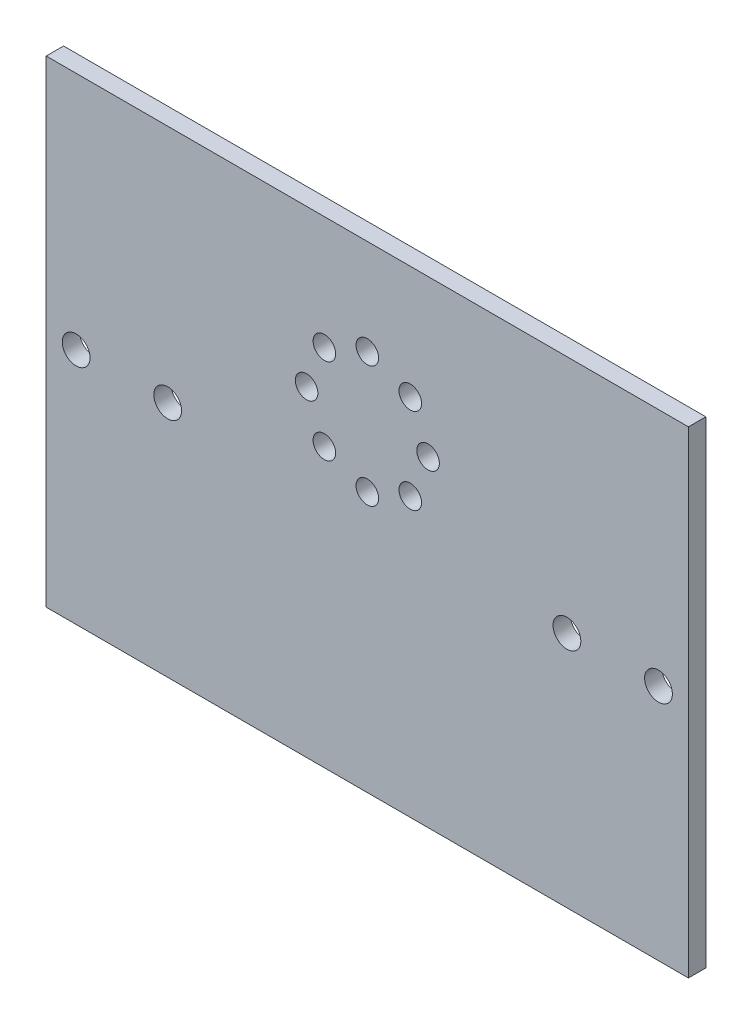
SolidWorks part; units mm, degrees
ref_plane "前基準面" through (0, 0, 0) normal (0, 0, 1) x (1, 0, 0)
ref_plane "上基準面" through (0, 0, 0) normal (0, 1, 0) x (1, 0, 0)
ref_plane "右基準面" through (0, 0, 0) normal (1, 0, 0) x (0, 0, -1)
sketch "草圖1" plane through (0, 0, 0) normal (0, 0, 1) x (1, 0, 0)
  line L1 (-37, 27.5) -> (37, 27.5)
  line L2 (-37, 27.5) -> (-37, -27.5)
  line L3 (-37, -27.5) -> (37, -27.5)
  line L4 (37, 27.5) -> (37, -27.5)
  line L5 (-37, 27.5) -> (37, -27.5) construction
  line L6 (-37, -27.5) -> (37, 27.5) construction
  point P0 (0, 0)
  dimension "D1" = 74
  dimension "D2" = 55
extrude "填料-伸長1" add sketch "草圖1" along normal blind 2
sketch "草圖2" plane through (0, 0, 2) normal (0, 0, 1) x (1, 0, 0)
  line L0 (-33.55, -0.1) -> (33.55, -0.1) construction
  line L1 (-37, 9.5) -> (37, 9.5) construction
  line L4 (0, 27.5) -> (0, -27.5) construction
  line L5 (37, 27.5) -> (-37, 27.5) construction
  line L6 (-37, -27.5) -> (37, -27.5) construction
  line L7 (37, -27.5) -> (37, 27.5) construction
  line L8 (-37, 27.5) -> (-37, -27.5) construction
  circle A0 centre (-33.55, -0.1) radius 1.6
  circle A1 centre (33.55, -0.1) radius 1.6
  circle A2 centre (-23, -0.1) radius 1.6
  circle A3 centre (23, -0.1) radius 1.6
  circle A4 centre (0, 2.5) radius 1.3
  circle A5 centre (-4.9497, 4.5503) radius 1.3
  circle A6 centre (-7, 9.5) radius 1.3
  circle A7 centre (-4.9497, 14.4497) radius 1.3
  circle A8 centre (0, 16.5) radius 1.3
  circle A9 centre (4.9497, 14.4497) radius 1.3
  circle A10 centre (7, 9.5) radius 1.3
  circle A11 centre (4.9497, 4.5503) radius 1.3
  point P8 (0, -0.1)
  point P11 (0, 0)
  point P40 (0, 9.5)
  point P43 (0, 9.5)
  dimension "D3" = 3.2
  dimension "D7" = 2.6
  dimension "D1" = 67.1
  dimension "D2" = 46
  dimension "D4" = 23
  dimension "D5" = 27.4
  dimension "D6" = 7
  dimension "D9" = 37
  dimension "D8" = 8
extrude "除料-伸長1" cut sketch "草圖2" against normal through all contours A0 | A2 | A3 | A1
extrude "除料-伸長2" cut sketch "草圖2<3>" against normal through all contours A4 | A11 | A10 | A9 | A7 | A6 | A5 | A8 region at (0, 2.5, 2) region at (-4.9497, 4.5503, 2) region at (-7, 9.5, 2) region at (-4.9497, 14.4497, 2) region at (4.9497, 14.4497, 2) region at (7, 9.5, 2) region at (4.9497, 4.5503, 2)
sketch "草圖2<3>" plane through (0, 0, 2) normal (0, 0, 1) x (1, 0, 0) same geometry as "草圖2"
